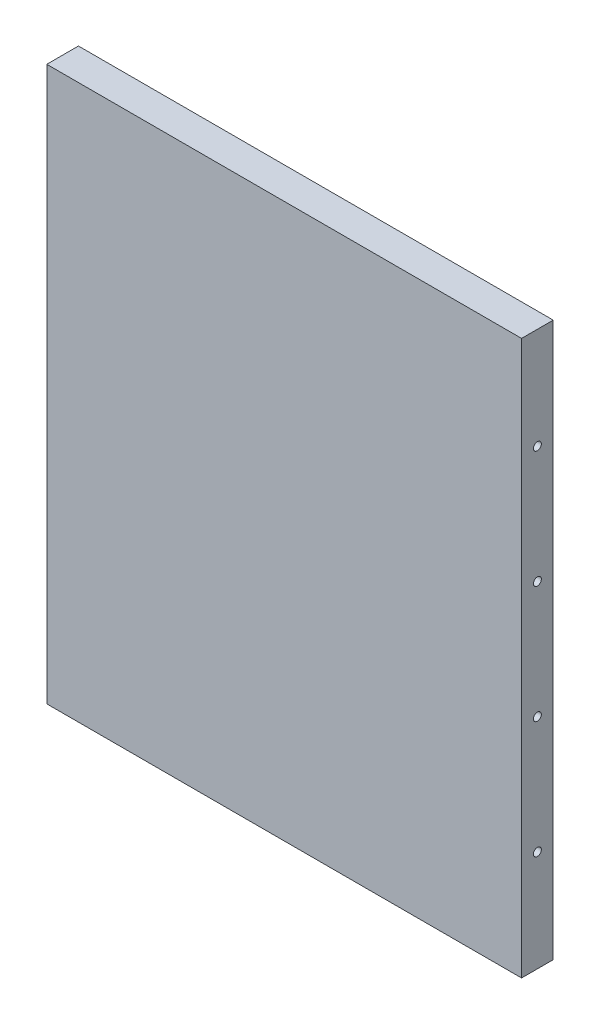
SolidWorks part; units mm, degrees
ref_plane "Ebene vorne" through (0, 0, 0) normal (0, 0, 1) x (1, 0, 0)
ref_plane "Ebene oben" through (0, 0, 0) normal (0, 1, 0) x (1, 0, 0)
ref_plane "Ebene rechts" through (0, 0, 0) normal (1, 0, 0) x (0, 0, -1)
sketch "Skizze1" plane through (0, 0, 0) normal (0, 0, 1) x (1, 0, 0)
  line L1 (-84.7009, 65.5769) -> (65.2991, 65.5769)
  line L2 (-84.7009, 65.5769) -> (-84.7009, -109.4231)
  line L3 (-84.7009, -109.4231) -> (65.2991, -109.4231)
  line L4 (65.2991, 65.5769) -> (65.2991, -109.4231)
  dimension "D1" = 150
  dimension "D2" = 175
extrude "Aufsatz-Linear austragen1" add sketch "Skizze1" along normal blind 10
sketch "Skizze2" plane through (-84.7009, 0, 0) normal (-1, 0, 0) x (0, 0, 1)
  line L0 (0, -21.9231) -> (10, -21.9231) construction
  line L1 (0, 65.5769) -> (0, -109.4231) construction
  line L2 (10, 65.5769) -> (10, -109.4231) construction
  line L3 (5, -40.4231) -> (5, -3.4231) construction
  line L4 (5, -3.4231) -> (5, 33.5769) construction
  line L5 (5, -40.4231) -> (5, -77.4231) construction
  circle A0 centre (5, 33.5769) radius 1.25
  circle A1 centre (5, -3.4231) radius 1.25
  circle A2 centre (5, -40.4231) radius 1.25
  circle A3 centre (5, -77.4231) radius 1.25
  point P8 (5, -21.9231)
  point P11 (5, -21.9231)
  dimension "D2" = 2.5
  dimension "D1" = 37
extrude "Schnitt-Linear austragen1" cut sketch "Skizze2" against normal blind 5
sketch "Skizze3" plane through (65.2991, 0, 0) normal (1, 0, 0) x (0, 0, -1)
  line L0 (-10, -21.9231) -> (0, -21.9231) construction
  line L1 (-5, -40.4231) -> (-5, -3.4231) construction
  line L2 (-5, -3.4231) -> (-5, 33.5769) construction
  line L3 (-5, -40.4231) -> (-5, -77.4231) construction
  line L4 (0, -109.4231) -> (0, 65.5769) construction
  line L5 (-10, -109.4231) -> (-10, 65.5769) construction
  circle A0 centre (-5, 33.5769) radius 1.25
  circle A1 centre (-5, -3.4231) radius 1.25
  circle A2 centre (-5, -40.4231) radius 1.25
  circle A3 centre (-5, -77.4231) radius 1.25
  point P4 (-5, -21.9231)
  point P7 (-5, -21.9231)
  point P12 (0, -21.9231)
  point P15 (-4.1745, 33.5769)
  point P16 (-10, -21.9231)
  dimension "D2" = 2.5
  dimension "D1" = 37
extrude "Schnitt-Linear austragen2" cut sketch "Skizze3" against normal blind 5
